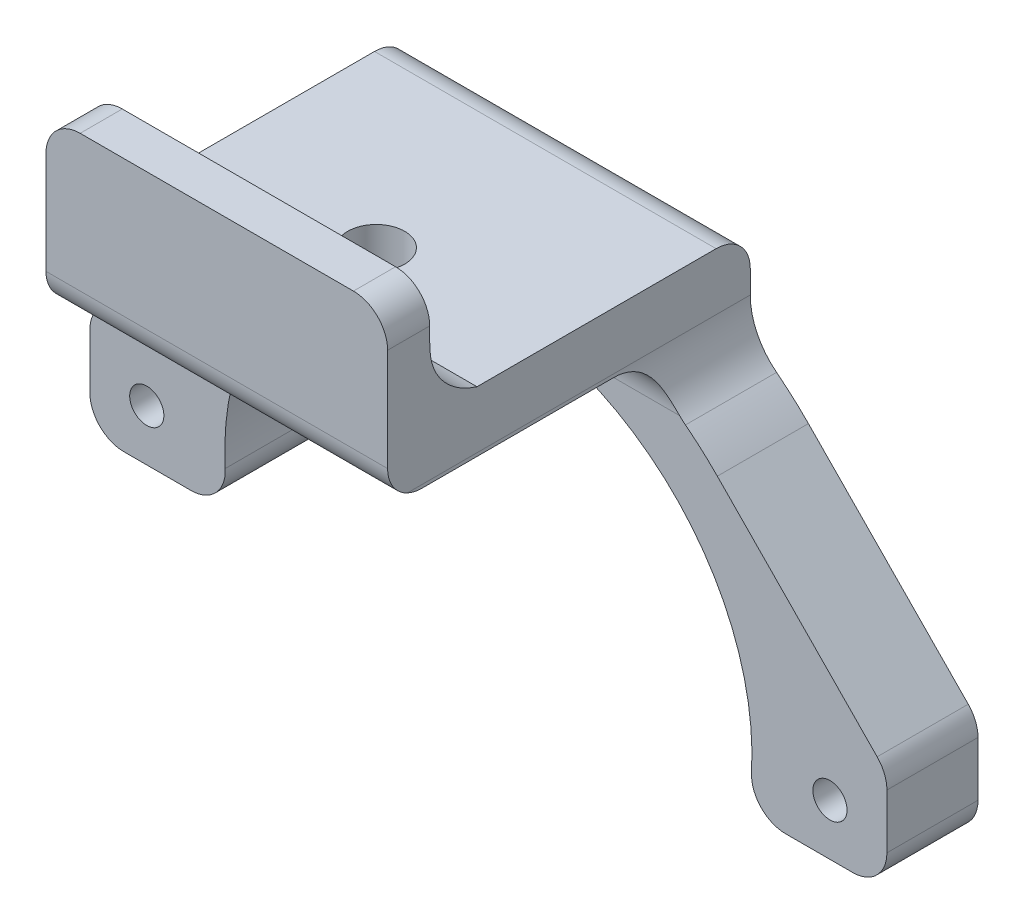
SolidWorks part; units mm, degrees
ref_plane "前视基准面" through (0, 0, 0) normal (0, 0, 1) x (1, 0, 0)
ref_plane "上视基准面" through (0, 0, 0) normal (0, 1, 0) x (1, 0, 0)
ref_plane "右视基准面" through (0, 0, 0) normal (1, 0, 0) x (0, 0, -1)
other "Configuration Table"
sketch "草图1" plane through (0, 0, 0) normal (0, 0, 1) x (1, 0, 0)
  line L0 (22.5555, 4.5) -> (75, 4.5) construction
  line L1 (-75, -4.5) -> (-22.5555, -4.5) construction
  line L2 (-75, -4.5) -> (-75, 4.5) construction
  line L3 (-75, 4.5) -> (-22.5555, 4.5) construction
  line L4 (75, -4.5) -> (75, 4.5) construction
  line L5 (-75, -4.5) -> (75, 4.5) construction
  line L6 (-75, 4.5) -> (75, -4.5) construction
  line L7 (22.5555, -4.5) -> (75, -4.5) construction
  line L8 (-70, 0) -> (-75, 0) construction
  line L9 (-27.788, -4.5) -> (-35, -4.5)
  line L10 (-35, -4.5) -> (-35, 4.5)
  line L11 (0, 20.75) -> (0, -20.75) construction
  line L12 (-35, 4.5) -> (-20.1078, 19.7003)
  line L13 (27.788, -4.5) -> (35, -4.5)
  line L14 (35, -4.5) -> (35, 4.5)
  line L15 (35, 4.5) -> (20.1078, 19.7003)
  line L16 (-27.788, -4.5) -> (-22.5555, -4.5)
  line L17 (22.5555, -4.5) -> (27.788, -4.5)
  circle A0 centre (0, 20.75) radius 1.5 construction
  circle A1 centre (14.6725, 14.6725) radius 1.5 construction
  circle A2 centre (20.75, 0) radius 1.5 construction
  circle A3 centre (14.6725, -14.6725) radius 1.5 construction
  circle A4 centre (0, -20.75) radius 1.5 construction
  circle A5 centre (-14.6725, -14.6725) radius 1.5 construction
  circle A6 centre (-20.75, 0) radius 1.5 construction
  circle A7 centre (-14.6725, 14.6725) radius 1.5 construction
  circle A8 centre (0, 0) radius 17.5 construction
  circle A9 centre (0, 0) radius 23 construction
  arc A10 (-22.5555, 4.5) -> (22.5555, 4.5) centre (0, 0) cw construction
  arc A11 (22.5555, -4.5) -> (-22.5555, -4.5) centre (0, 0) cw construction
  circle A12 centre (-70, 0) radius 1.5 construction
  circle A13 centre (-50, 0) radius 1.5 construction
  circle A14 centre (-30, 0) radius 1.5
  circle A15 centre (-10, 0) radius 1.5 construction
  circle A17 centre (30, 0) radius 1.5
  circle A18 centre (50, 0) radius 1.5 construction
  circle A19 centre (70, 0) radius 1.5 construction
  circle A21 centre (10, 0) radius 1.5 [skipped]
  circle A22 centre (90, 0) radius 1.5 [skipped]
  circle A23 centre (0, 0) radius 23.15
  circle A24 centre (0, 0) radius 28.15
  point P19 (0, 0)
  point P25 (22.5555, 4.5)
  point P26 (22.5555, -4.5)
  point P27 (-22.5555, 4.5)
  point P28 (-22.5555, -4.5)
  dimension "D2" = 3
  dimension "D4" = 35
  dimension "D5" = 46
  dimension "D8" = 3
  dimension "D12" = 46.3
  dimension "D1" = 20.75
  dimension "D3" = 8
  dimension "D6" = 9
  dimension "D7" = 150
  dimension "D9" = 5
  dimension "D11" = 20
  dimension "D14" = 35
  dimension "D13" = 5
  dimension "D10" = 9
extrude "凸台-拉伸1" add sketch "草图1" along normal blind 8 contours A24 L12 L10 L9 A14 | A24 L16 A23 L17 | A24 L13 L14 L15 A17 region at (-26.2109, 8.3183, 0) region at (-30.5148, 3.5496, 0) region at (30.5148, 3.5496, 0)
sketch "草图2" plane through (0, 0, 8) normal (0, 0, 1) x (1, 0, 0)
  line L0 (-15, 28.15) -> (15, 28.15)
  line L1 (-15, 28.15) -> (15, 28.15)
  line L2 (-15, 28.15) -> (-15, 27.15)
  line L3 (15, 28.15) -> (15, 27.15)
  line L4 (-15, 27.15) -> (-7.4364, 27.15)
  line L5 (-15, 27.15) -> (-15, 23.8206)
  line L6 (-35, -4.5) -> (-22.7084, -4.5)
  line L7 (22.7084, -4.5) -> (35, -4.5)
  line L8 (35, -4.5) -> (35, 4.5)
  line L9 (35, 4.5) -> (20.1078, 19.7003)
  line L10 (-20.1078, 19.7003) -> (-35, 4.5)
  line L11 (-35, 4.5) -> (-35, -4.5)
  line L12 (-35, -4.5) -> (-22.7084, -4.5)
  line L13 (22.7084, -4.5) -> (35, -4.5)
  line L14 (35, -4.5) -> (35, 4.5)
  line L15 (35, 4.5) -> (20.1078, 19.7003)
  line L16 (-20.1078, 19.7003) -> (-35, 4.5)
  line L17 (-35, 4.5) -> (-35, -4.5)
  line L18 (15, 27.15) -> (15, 23.8206)
  line L19 (-15, 28.15) -> (15, 28.15)
  line L20 (-15, 28.15) -> (-15, 31.95)
  line L21 (15, 28.15) -> (15, 31.95)
  line L22 (-15, 31.95) -> (15, 31.95)
  line L23 (7.4364, 27.15) -> (15, 27.15)
  arc A2 (22.7084, -4.5) -> (-22.7084, -4.5) centre (0, 0) ccw
  arc A3 (20.1078, 19.7003) -> (-20.1078, 19.7003) centre (0, 0) ccw
  arc A4 (22.7084, -4.5) -> (-22.7084, -4.5) centre (0, 0) ccw
  arc A5 (20.1078, 19.7003) -> (-20.1078, 19.7003) centre (0, 0) ccw
  point P11 (0, 28.15)
  arc M18 (20.1078, 19.7003) -> (-20.1078, 19.7003) centre (0, 0) ccw
  dimension "D2" = 30
  dimension "D3" = 1
  dimension "D4" = 3.8
  dimension "D1" = 0
extrude "凸台-拉伸2" add sketch "草图2" against normal blind 8 contours L4 L5 M18 | L23 L18 M18 | L23 L3 L0 M18 | L2 L4 L0 M18 | L22 L20 L0 L21 region at (0, 30.05, 8) region at (-9.8351, 27.6993, 8) region at (9.8351, 27.6993, 8) region at (-12.6655, 26.1085, 8) region at (12.6655, 26.1085, 8)
sketch "草图3" plane through (0, 0, 8) normal (0, 0, 1) x (1, 0, 0)
  line L0 (-15, 26.65) -> (15, 26.65)
  line L1 (-15, 23.8206) -> (-15, 31.95) construction
  line L2 (15, 31.95) -> (15, 23.8206) construction
  line L3 (-15, 31.95) -> (15, 31.95) construction
  line L13 (-35, -4.5) -> (-22.7084, -4.5)
  line L14 (22.7084, -4.5) -> (35, -4.5)
  line L15 (35, -4.5) -> (35, 4.5)
  line L16 (35, 4.5) -> (20.1078, 19.7003)
  line L17 (15, 23.8206) -> (15, 31.95)
  line L18 (15, 31.95) -> (-15, 31.95)
  line L19 (-15, 31.95) -> (-15, 23.8206)
  line L20 (-20.1078, 19.7003) -> (-35, 4.5)
  line L21 (-35, 4.5) -> (-35, -4.5)
  line L22 (-35, -4.5) -> (-22.7084, -4.5)
  line L23 (22.7084, -4.5) -> (35, -4.5)
  line L24 (35, -4.5) -> (35, 4.5)
  line L25 (35, 4.5) -> (20.1078, 19.7003)
  line L26 (15, 23.8206) -> (15, 31.95)
  line L27 (15, 31.95) -> (-15, 31.95)
  line L28 (-15, 31.95) -> (-15, 23.8206)
  line L29 (-20.1078, 19.7003) -> (-35, 4.5)
  line L30 (-35, 4.5) -> (-35, -4.5)
  arc A3 (22.7084, -4.5) -> (-22.7084, -4.5) centre (0, 0) ccw
  arc A4 (20.1078, 19.7003) -> (15, 23.8206) centre (0, 0) ccw
  arc A5 (-15, 23.8206) -> (-20.1078, 19.7003) centre (0, 0) ccw
  arc A6 (22.7084, -4.5) -> (-22.7084, -4.5) centre (0, 0) ccw
  arc A7 (20.1078, 19.7003) -> (15, 23.8206) centre (0, 0) ccw
  arc A8 (-15, 23.8206) -> (-20.1078, 19.7003) centre (0, 0) ccw
  line M20 (15, 23.8206) -> (15, 31.95)
  line M21 (15, 31.95) -> (-15, 31.95)
  line M22 (-15, 31.95) -> (-15, 23.8206)
  dimension "D1" = 5.3
  dimension "D2" = 0
extrude "凸台-拉伸3" add sketch "草图3" along normal blind 20 contours L0 M22 M20 M21 region at (0, 29.3, 8)
sketch "草图4" plane through (0, 31.95, 0) normal (0, 1, 0) x (1, 0, 0)
  line L0 (15, -28) -> (-15, -28) construction
  circle A0 centre (0, -17.85) radius 2.5
  dimension "D1" = 5
  dimension "D2" = 10.15
extrude "切除-拉伸1" cut sketch "草图4" against normal through all
sketch "草图5" plane through (-15, 0, 0) normal (-1, 0, 0) x (0, 0, 1)
  line L0 (28.15, 37.3878) -> (28.15, 41.65)
  line L1 (28.15, 41.65) -> (31.05, 41.65)
  line L2 (31.05, 41.65) -> (31.05, 26.65)
  line L3 (31.05, 26.65) -> (28, 26.65)
  line L4 (31.05, 41.65) -> (31.05, 26.65)
  line L5 (31.05, 41.65) -> (31.85, 41.65)
  line L6 (8, 23.8206) -> (8, 26.65)
  line L7 (8, 26.65) -> (28, 26.65)
  line L8 (28, 26.65) -> (28, 31.95)
  line L9 (28, 31.95) -> (0, 31.95)
  line L10 (0, 31.95) -> (0, 23.8206)
  line L11 (0, 23.8206) -> (8, 23.8206)
  line L12 (8, 23.8206) -> (8, 26.65)
  line L13 (8, 26.65) -> (28, 26.65)
  line L14 (28, 26.65) -> (28, 31.95)
  line L15 (28, 31.95) -> (0, 31.95)
  line L16 (0, 31.95) -> (0, 23.8206)
  line L17 (0, 23.8206) -> (8, 23.8206)
  line L18 (31.05, 26.65) -> (31.85, 26.65)
  line L19 (31.85, 41.65) -> (31.85, 26.65)
  spline S1 degree 3 poles (23.6396, 31.9411) (24.169, 32.1027) (25.3216, 32.4982) (26.9832, 33.7994) (27.8144, 35.3263) (28.0278, 36.5353) (28.0434, 37.1144) (28.05, 37.3902) knots 0.000013 0.000013 0.000013 0.000013 0.235515 0.493921 0.752327 0.88153 1 1 1 1 weights 1 1 1 1 1 1 1 1 construction
  spline S2 degree 1 poles (23.6688, 31.8454) (28.15, 37.3878) knots 0 0 1 1 construction
  spline S3 degree 3 poles (23.6688, 31.8454) (23.7533, 31.8712) (23.8883, 31.9133) (24.1761, 32.0076) (24.6681, 32.1837) (25.7028, 32.6578) (27.0859, 33.7777) (27.9016, 35.2824) (28.127, 36.5077) (28.1429, 37.0917) (28.15, 37.3878) knots 0.000013 0.000013 0.000013 0.000013 0.036373 0.060613 0.125011 0.25001 0.500007 0.750003 0.875002 1 1 1 1
  point P14 (24, 31.95)
  line M11 (28, 26.65) -> (28, 31.95)
  line M12 (28, 31.95) -> (0, 31.95)
  dimension "D3" = 3.05
  dimension "D4" = 15
  dimension "D5" = 4
  dimension "D6" = 2.9
  dimension "D7" = 0.8
  dimension "D1" = 0
  dimension "D2" = 0.1
extrude "凸台-拉伸4" add sketch "草图5" against normal up to surface (30 mm away) contours S3 L3 L2 L1 L0 M12 M11 | L19 L5 L2 L18 region at (-15, 33.9566, 29.2844) region at (-15, 34.15, 31.45) up to face at (15, 27.4735, 12)
fillet "圆角1" radius 4 1 edges at (0, 26.65, 8)
fillet "圆角2" radius 6 2 edges at (15, 23.8206, 4.0876) (-15, 23.8206, 4.0876)
fillet "圆角3" radius 3 8 edges at (22.7084, -4.5, 4) (-22.7084, -4.5, 4) (35, -4.5, 4) (-35, -4.5, 4) (0, 31.95, 0) (35, 4.5, 4) (-35, 4.5, 4) (0, 26.65, 31.85)
fillet "圆角4" radius 3 2 edges at (15, 41.65, 30) (-15, 41.65, 30)
